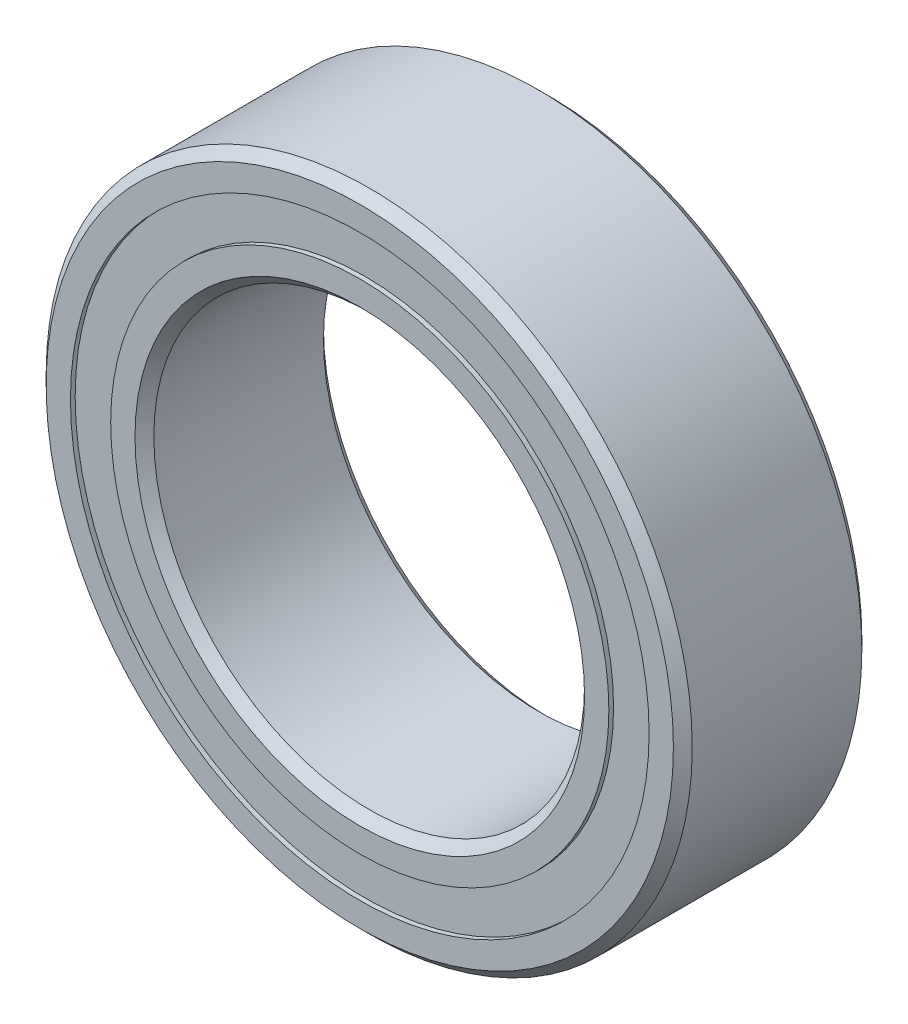
SolidWorks part; units mm, degrees
ref_plane "Front Plane" through (0, 0, 0) normal (0, 0, 1) x (1, 0, 0)
ref_plane "Top Plane" through (0, 0, 0) normal (0, 1, 0) x (1, 0, 0)
ref_plane "Right Plane" through (0, 0, 0) normal (1, 0, 0) x (0, 0, -1)
sketch "Sketch1" plane through (0, 0, 0) normal (1, 0, 0) x (0, 0, -1)
  line L0 (-1.75, 0) -> (1.75, 0) construction
  line L1 (0, 6) -> (0, -6) construction
  line L2 (1.575, 6) -> (-1.575, 6)
  line L3 (-1.575, 6) -> (-1.75, 5.825)
  line L4 (-1.75, 5.825) -> (-1.75, 5.3736)
  line L5 (-1.75, 5.3736) -> (-0.7778, 5.3736)
  line L6 (1.75, 5.3736) -> (0.7778, 5.3736)
  line L7 (1.75, 5.825) -> (1.75, 5.3736)
  line L8 (1.575, 6) -> (1.75, 5.825)
  line L9 (0, 6) -> (0, 5) construction
  line L10 (0, 5) -> (0, 4) construction
  arc A0 (-0.7778, 5.3736) -> (0.7778, 5.3736) centre (0, 5) cw
  point P14 (0, 4)
  dimension "Width" = 3.5
  dimension "OD" = 12
  dimension "D1" = 45
  dimension "D2" = 0.175
  dimension "Shaft Dia" = 8
  dimension "D3" = 1.5556
  dimension "D4" = 0.3736
revolve "Revolve1" add sketch "Sketch1" angle 360 about L0
sketch "Sketch3" plane through (0, 0, 0) normal (1, 0, 0) x (0, 0, -1)
  line L0 (-1.75, 4.6264) -> (-0.7778, 4.6264)
  line L1 (0, 6) -> (0, -6) construction
  line L2 (-1.75, 5.825) -> (-1.75, 5.3736) construction
  line L3 (-1.75, 4.6264) -> (-1.75, 4.175)
  line L4 (-1.575, 6) -> (-1.75, 5.825) construction
  line L5 (-1.75, 4.175) -> (-1.575, 4)
  line L6 (-1.575, 4) -> (1.575, 4)
  line L7 (1.575, 6) -> (1.575, -6) construction
  line L8 (1.575, 4) -> (1.75, 4.175)
  line L9 (1.75, -5.825) -> (1.75, 5.825) construction
  line L10 (1.75, 4.175) -> (1.75, 4.6264)
  line L11 (1.75, 4.6264) -> (0.7778, 4.6264)
  line L13 (1.575, 6) -> (1.75, 5.825) construction
  arc A0 (0.7778, 5.3736) -> (-0.7778, 5.3736) centre (0, 5) ccw construction
  arc A1 (0.7778, 4.6264) -> (-0.7778, 4.6264) centre (0, 5) cw
revolve "Revolve3" add sketch "Sketch3" angle 360 about L0
sketch "Sketch4" plane through (0, 0, 0) normal (1, 0, 0) x (0, 0, -1)
  line L0 (-0.8629, 5) -> (0.8629, 5)
  arc A2 (-0.8629, 5) -> (0.8629, 5) centre (0, 5) cw
  arc A3 (0.7778, 5.3736) -> (-0.7778, 5.3736) centre (0, 5) ccw construction
revolve "Revolve4" add sketch "Sketch4" angle 360 about L0
ref_axis "Axis1" through (0, 0, -1.75) along (0, 0, 1)
pattern_circular "CirPattern1" count 12 every 30 about axis through (0, 0, -1.75) along (0, 0, 1) of bodies 104
sketch "Sketch5" plane through (0, 0, 0) normal (1, 0, 0) x (0, 0, -1)
  line L0 (-1.75, 5.3736) -> (-0.7778, 5.3736) construction
  line L1 (-1.6625, 5.3736) -> (-0.8629, 5.3736)
  line L2 (-1.6625, 5.3736) -> (-1.6625, 4.6264)
  line L3 (-1.6625, 4.6264) -> (-0.8629, 4.6264)
  line L4 (-0.8629, 5.3736) -> (-0.8629, 4.6264)
  line L5 (-1.75, 4.6264) -> (-0.7778, 4.6264) construction
  line L6 (1.75, 5.3736) -> (0.7778, 5.3736) construction
  line L7 (1.6625, 5.3736) -> (0.8629, 5.3736)
  line L8 (1.6625, 5.3736) -> (1.6625, 4.6264)
  line L9 (1.6625, 4.6264) -> (0.8629, 4.6264)
  line L10 (0.8629, 5.3736) -> (0.8629, 4.6264)
  line L11 (1.75, 4.6264) -> (0.7778, 4.6264) construction
  line L12 (-1.575, 6) -> (-1.75, 5.825) construction
  point P18 (-1.6625, 5.9125)
revolve "Revolve5" add sketch "Sketch5" angle 360 about L0
sketch "Sketch6" plane through (0, 0, 0) normal (1, 0, 0) x (0, 0, -1)
  line L0 (1.75, 0) -> (-1.75, 0) construction
  line L1 (1.75, 5.3736) -> (0.65, 5.3736)
  line L2 (1.75, 5.3736) -> (1.75, 9.5)
  line L3 (1.75, 9.5) -> (0.65, 9.5)
  line L4 (0.65, 5.3736) -> (0.65, 9.5)
  dimension "Th" = 1.1
  dimension "Flange OD" = 19
revolve "Revolve6" [suppressed] add sketch "Sketch6" angle 360 about L0
equation "\"D2@Sketch1\" = \"Width@Sketch1\"*.05"
equation "\"D3@Sketch1\" = \"Width@Sketch1\"/2.25"
equation "\"D4@Sketch1\" = (((\"OD@Sketch1\"-\"Width@Sketch1\")/2)/3.25)/3.5"
equation "\"D2@CirPattern1\" = 360/\"Balls@CirPattern1\""
